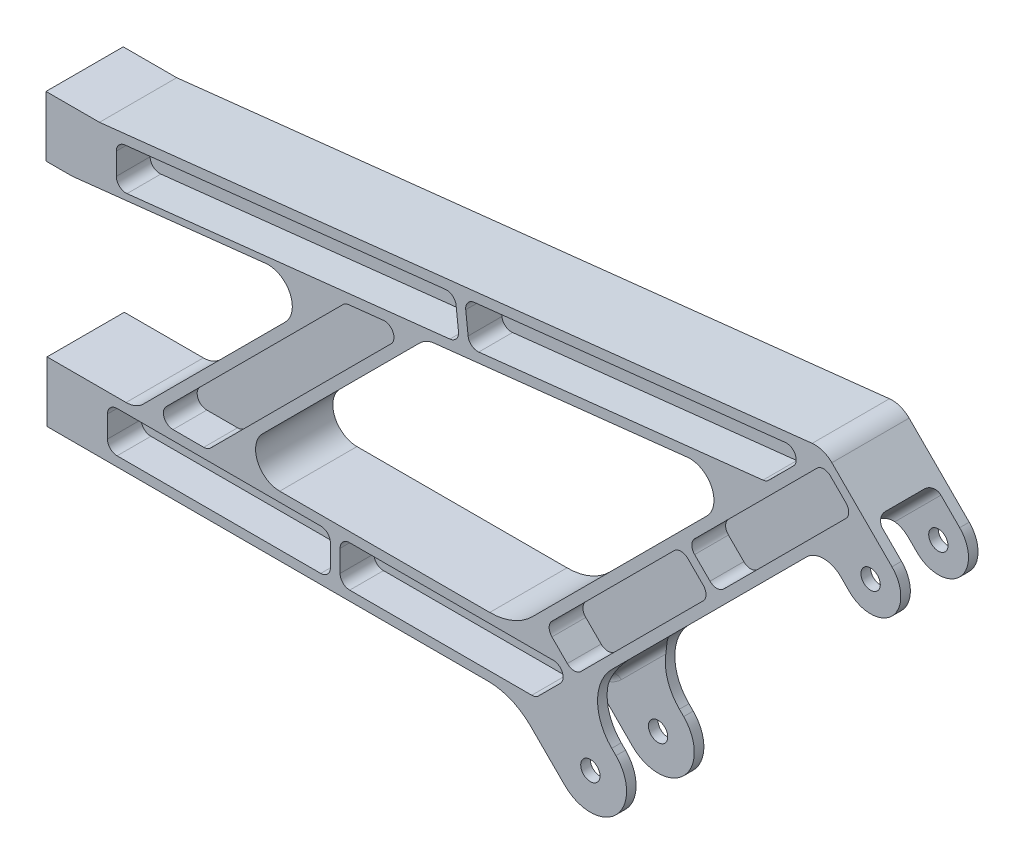
SolidWorks part; units mm, degrees
material "6061-T6 (SS)"
ref_plane "Front Plane" through (0, 0, 0) normal (0, 0, 1) x (1, 0, 0)
ref_plane "Top Plane" through (0, 0, 0) normal (0, 1, 0) x (1, 0, 0)
ref_plane "Right Plane" through (0, 0, 0) normal (1, 0, 0) x (0, 0, -1)
sketch "Sketch1" plane through (0, 0, 0) normal (0, 0, 1) x (1, 0, 0)
  line L1 (-157.7639, -90.8401) -> (-244.7728, -90.8401)
  line L2 (-67.8181, -11.2496) -> (-140.0863, -83.5177)
  line L3 (-16.0497, 33.7315) -> (8.8396, 8.8381)
  line L4 (-12.3744, -5.3033) -> (-8.8388, -8.8388)
  line L5 (-26.5165, -5.3033) -> (-107.2487, -86.0355)
  line L6 (-140.8326, -123.1624) -> (-126.6942, -137.3008)
  line L7 (-158.5102, -115.8401) -> (-341.1373, -115.8401)
  line L8 (-341.1373, -115.8401) -> (-341.1373, -90.8401)
  line L9 (-308.4124, -90.8401) -> (-341.1373, -90.8401)
  line L11 (-341.5776, -20.8403) -> (-331.2717, -20.8403)
  line L12 (-341.5776, -20.8403) -> (-341.5776, 4.1597)
  line L13 (-341.5776, 4.1597) -> (-319.4176, 4.1597)
  line L14 (-107.2487, -114.3198) -> (-105.481, -116.0876)
  line L15 (-319.4176, 4.1597) -> (-24.2138, 36.6012)
  line L17 (-301.3413, -87.9111) -> (-242.4814, -29.0512)
  line L18 (-75.9816, 5.7616) -> (-180.7131, -5.7479)
  line L19 (-251.8438, -73.769) -> (-186.6918, -8.6169)
  line L20 (-250.6448, -12.04) -> (-330.1793, -20.7804)
  arc A4 (8.8388, -8.8388) -> (8.8396, 8.8381) centre (0, 0) ccw
  arc A5 (-8.8388, -8.8388) -> (8.8388, -8.8388) centre (0, 0) ccw
  arc A6 (-12.3744, -5.3033) -> (-26.5165, -5.3033) centre (-19.4454, -12.3744) ccw
  arc A7 (-107.2487, -86.0355) -> (-107.2487, -114.3198) centre (-93.1066, -100.1777) ccw
  arc A8 (-105.481, -137.3008) -> (-105.481, -116.0876) centre (-116.0876, -126.6942) ccw
  arc A9 (-126.6942, -137.3008) -> (-105.481, -137.3008) centre (-116.0876, -126.6942) ccw
  circle A12 centre (-116.0876, -126.6942) radius 4
  circle A13 centre (0, 0) radius 4
  arc A15 (-158.5102, -115.8401) -> (-140.8326, -123.1624) centre (-158.5102, -140.8401) cw
  arc A16 (-157.7639, -90.8401) -> (-140.0863, -83.5177) centre (-157.7639, -65.8401) ccw
  arc A20 (-67.8181, -11.2496) -> (-75.9816, 5.7616) centre (-74.8892, -4.1785) ccw
  arc A21 (-16.0497, 33.7315) -> (-24.2138, 36.6012) centre (-23.1214, 26.661) ccw
  arc A22 (-186.6918, -8.6169) -> (-180.7131, -5.7479) centre (-179.6207, -15.688) cw
  arc A23 (-244.7728, -90.8401) -> (-251.8438, -73.769) centre (-244.7728, -80.8401) cw
  arc A24 (-330.1793, -20.7804) -> (-331.2717, -20.8403) centre (-331.2717, -10.8403) cw
  arc A25 (-308.4124, -90.8401) -> (-301.3413, -87.9111) centre (-308.4124, -80.8401) ccw
  arc A26 (-250.6448, -12.04) -> (-242.4814, -29.0512) centre (-249.5525, -21.9802) cw
  dimension "D2" = 25
  dimension "D3" = 25
  dimension "D7" = 10
  dimension "D6" = 25
  dimension "D1" = 25
  dimension "D4" = 25
  dimension "D5" = 25
  dimension "D8" = 119.9998
extrude "Boss-Extrude1" add sketch "Sketch1" along normal blind 32
sketch "Sketch2" plane through (0, 0, 32) normal (0, 0, 1) x (1, 0, 0)
  line L0 (-107.2487, -86.0355) -> (-26.5165, -5.3033) construction
  line L1 (-137.5386, -110.6685) -> (-128.5386, -101.6685)
  line L2 (-131.367, -94.8401) -> (-215.77, -94.8401)
  line L3 (-67.8181, -11.2496) -> (-140.0863, -83.5177) construction
  line L4 (-107.2487, -86.0355) -> (-26.5165, -5.3033)
  line L5 (-67.8181, -11.2496) -> (-140.0863, -83.5177)
  line L6 (-22.272, 28.6397) -> (-72.893, -21.9813)
  line L7 (-119.9767, -93.1066) -> (-69.3575, -42.4874)
  line L8 (-131.9975, -86.7426) -> (-125.6335, -93.1066)
  line L9 (-10.2515, 22.275) -> (-16.6149, 28.6394)
  line L10 (-64.9897, -14.078) -> (-137.2579, -86.3462) construction
  line L11 (-110.0772, -83.2071) -> (-29.3449, -2.4749) construction
  line L12 (-341.1373, -115.8401) -> (-158.5102, -115.8401) construction
  line L13 (-341.1373, -115.8401) -> (-158.5102, -115.8401)
  line L14 (-312.1373, -111.8401) -> (-227.77, -111.8401)
  line L15 (-341.1373, -111.8401) -> (-158.5102, -111.8401) construction
  line L16 (-341.1373, -90.8401) -> (-341.1373, -115.8401) construction
  line L17 (-316.1373, -98.8401) -> (-316.1373, -107.8401)
  line L18 (-157.7639, -90.8401) -> (-244.7728, -90.8401) construction
  line L19 (8.8396, 8.8381) -> (-16.0497, 33.7315) construction
  line L20 (-140.8326, -123.1624) -> (-126.6942, -137.3008) construction
  line L21 (-65.1149, -38.2448) -> (-77.1357, -26.224) construction
  line L22 (-72.893, -27.6382) -> (-66.5291, -34.0022)
  line L23 (-75.7215, -30.4666) -> (-69.3575, -36.8306)
  line L24 (-81.3783, -30.4666) -> (-131.9975, -81.0858)
  line L25 (-60.8722, -34.0022) -> (-10.2517, 16.6183)
  line L26 (-221.77, -94.8401) -> (-221.77, -111.8401) construction
  line L27 (-219.77, -98.8401) -> (-219.77, -107.8401)
  line L28 (-223.77, -98.8401) -> (-223.77, -107.8401)
  line L29 (-215.77, -111.8401) -> (-140.367, -111.8401)
  line L30 (-227.77, -94.8401) -> (-312.1373, -94.8401)
  line L38 (-308.8907, 1.2925) -> (-176.1091, 15.8845)
  line L39 (-24.2138, 36.6012) -> (-319.4176, 4.1597) construction
  line L40 (-308.0168, -15.7138) -> (-174.2521, -1.0137)
  line L41 (-75.9816, 5.7616) -> (-180.7131, -5.7479) construction
  line L42 (-312.4538, -2.6836) -> (-312.4538, -11.7378)
  line L43 (-32.0118, 24.5568) -> (-42.1838, 14.3847)
  line L44 (-170.145, 16.5399) -> (-168.288, -0.3583) construction
  line L45 (-171.6961, 12.3454) -> (-170.713, 3.3993)
  line L46 (-167.7201, 12.7824) -> (-166.7369, 3.8362)
  line L47 (-164.181, 17.1954) -> (-35.2771, 31.3613)
  line L48 (-162.3239, 0.2971) -> (-44.5753, 13.2371)
  line L49 (-218.5658, -10.7925) -> (-291.7849, -84.0116)
  line L50 (-242.4814, -29.0512) -> (-301.3413, -87.9111) construction
  line L51 (-198.6096, -14.8779) -> (-273.4002, -89.6685)
  line L52 (-186.6918, -8.6169) -> (-251.8438, -73.769) construction
  line L53 (-216.1743, -9.6449) -> (-201.875, -8.0734)
  line L54 (-288.9565, -90.8401) -> (-276.2286, -90.8401)
  line L55 (-341.5776, 4.1597) -> (-341.5776, -20.8403) construction
  arc A0 (-22.272, 28.6397) -> (-16.6149, 28.6394) centre (-19.4436, 25.8113) cw
  arc A1 (-10.2517, 16.6183) -> (-10.2515, 22.275) centre (-13.0801, 19.4468) ccw
  arc A2 (-119.9767, -93.1066) -> (-125.6335, -93.1066) centre (-122.8051, -90.2782) cw
  arc A3 (-131.9975, -81.0858) -> (-131.9975, -86.7426) centre (-129.169, -83.9142) ccw
  arc A4 (-312.1373, -111.8401) -> (-316.1373, -107.8401) centre (-312.1373, -107.8401) cw
  arc A5 (-312.1373, -94.8401) -> (-316.1373, -98.8401) centre (-312.1373, -98.8401) ccw
  arc A6 (-140.367, -111.8401) -> (-137.5386, -110.6685) centre (-140.367, -107.8401) ccw
  arc A7 (-128.5386, -101.6685) -> (-131.367, -94.8401) centre (-131.367, -98.8401) ccw
  arc A8 (-75.7215, -30.4666) -> (-81.3783, -30.4666) centre (-78.5499, -33.295) ccw
  arc A9 (-69.3575, -36.8306) -> (-69.3575, -42.4874) centre (-72.1859, -39.659) cw
  arc A10 (-66.5291, -34.0022) -> (-60.8722, -34.0022) centre (-63.7006, -31.1737) ccw
  arc A11 (-72.893, -27.6382) -> (-72.893, -21.9813) centre (-70.0646, -24.8098) cw
  arc A12 (-223.77, -107.8401) -> (-227.77, -111.8401) centre (-227.77, -107.8401) cw
  arc A13 (-219.77, -107.8401) -> (-215.77, -111.8401) centre (-215.77, -107.8401) ccw
  arc A14 (-219.77, -98.8401) -> (-215.77, -94.8401) centre (-215.77, -98.8401) cw
  arc A15 (-223.77, -98.8401) -> (-227.77, -94.8401) centre (-227.77, -98.8401) ccw
  arc A20 (-44.5753, 13.2371) -> (-42.1838, 14.3847) centre (-45.0122, 17.2132) ccw
  arc A21 (-35.2771, 31.3613) -> (-32.0118, 24.5568) centre (-34.8402, 27.3852) cw
  arc A22 (-166.7369, 3.8362) -> (-162.3239, 0.2971) centre (-162.7609, 4.2732) ccw
  arc A23 (-167.7201, 12.7824) -> (-164.181, 17.1954) centre (-163.744, 13.2193) cw
  arc A24 (-170.713, 3.3993) -> (-174.2521, -1.0137) centre (-174.6891, 2.9623) cw
  arc A25 (-171.6961, 12.3454) -> (-176.1091, 15.8845) centre (-175.6722, 11.9085) ccw
  arc A26 (-308.0168, -15.7138) -> (-312.4538, -11.7378) centre (-308.4538, -11.7378) cw
  arc A27 (-308.8907, 1.2925) -> (-312.4538, -2.6836) centre (-308.4538, -2.6836) ccw
  arc A28 (-198.6096, -14.8779) -> (-201.875, -8.0734) centre (-201.438, -12.0495) ccw
  arc A29 (-218.5658, -10.7925) -> (-216.1743, -9.6449) centre (-215.7374, -13.6209) cw
  arc A30 (-273.4002, -89.6685) -> (-276.2286, -90.8401) centre (-276.2286, -86.8401) cw
  arc A31 (-288.9565, -90.8401) -> (-291.7849, -84.0116) centre (-288.9565, -86.8401) cw
  point P34 (-316.1373, -111.8401)
  point P53 (-78.5499, -27.6382)
  point P58 (-63.7006, -36.8306)
  point P69 (-223.77, -111.8401)
  point P72 (-219.77, -111.8401)
  point P75 (-219.77, -94.8401)
  point P78 (-223.77, -94.8401)
  point P117 (-166.3, -0.1398)
  point P120 (-168.157, 16.7584)
  point P123 (-170.276, -0.5768)
  point P126 (-172.1331, 16.3215)
  dimension "D2" = 4
  dimension "D6" = 4
  dimension "D11" = 4
  dimension "D13" = 4
  dimension "D16" = 4
  dimension "D22" = 4
  dimension "D19" = 4
  dimension "D4" = 25
  dimension "D5" = 4
  dimension "D7" = 4
  dimension "D8" = 4
  dimension "D9" = 32
  dimension "D10" = 2
  dimension "D12" = 2
  dimension "D14" = 4
  dimension "D15" = 4
  dimension "D17" = 4
  dimension "D18" = 4
  dimension "D20" = 4
  dimension "D21" = 2
  dimension "D23" = 4
  dimension "D1" = 4
  dimension "D3" = 4
extrude "Cut-Extrude1" cut sketch "Sketch2" against normal blind 14 contours L38 A27 L42 A26 L40 A24 L45 A25 | A23 L46 A22 L48 A20 L43 A21 L47 | A31 L54 A30 L51 A28 L53 A29 L49 | A11 L22 A10 L25 A1 L9 A0 L6 | A9 L23 A8 L24 A3 L8 A2 L7 | A14 L27 A13 L29 A6 L1 A7 L2 | L28 A15 L30 A5 L17 A4 L14 A12 region at (-175.3079, -103.1533, 32) region at (-41.5723, -2.6814, 32) region at (-100.6775, -61.7866, 32) region at (-269.9537, -103.3401, 32) region at (-241.8227, 0.0982, 32) region at (-100.9045, 15.7508, 32) region at (-245.4094, -49.7028, 32)
ref_plane "Plane1" through (0, 0, 16) normal (0, 0, 1) x (1, 0, 0)
mirror "Mirror1" about plane through (0, 0, 16) normal (0, 0, 1) of "Cut-Extrude1"
sketch "Sketch3" plane through (0, 0, 16) normal (0, 0, 1) x (1, 0, 0)
  line L0 (-158.5102, -115.8401) -> (-141.1954, -115.8401)
  line L1 (-98.969, -77.7558) -> (-134.1243, -112.9111)
  line L2 (-107.2487, -86.0355) -> (-26.5165, -5.3033) construction
  line L3 (-158.5102, -115.8401) -> (-116.5971, -149.2186)
  line L4 (-116.5971, -149.2186) -> (-66.3597, -110.0186)
  line L5 (-66.3597, -110.0186) -> (-98.969, -77.7558)
  line L6 (-29.0156, -7.8024) -> (7.8698, 29.083)
  line L7 (7.8698, 29.083) -> (26.3533, -15.3879)
  line L8 (26.3533, -15.3879) -> (-12.041, -17.819)
  line L9 (-12.041, -17.819) -> (-29.0156, -7.8024)
  arc A0 (-134.1243, -112.9111) -> (-141.1954, -115.8401) centre (-141.1954, -105.8401) cw
  dimension "D1" = 10
extrude "Cut-Extrude2" cut sketch "Sketch3" against normal blind 12.0515 and the other way blind 12.0515
sketch "Sketch5" plane through (0, 0, 16) normal (0, 0, 1) x (1, 0, 0)
  line L0 (0, -24.7236) -> (0, -90.9031)
fillet "Fillet1" radius 4 2 edges at (-14.1417, 7.0715, 28.0515) (-14.1417, 7.0715, 3.9485)
fillet "Fillet2" radius 4 6 edges at (-149.8528, -115.8401, 3.9485) (-137.3686, -115.0789, 3.9485) (-149.8528, -115.8401, 28.0515) (-137.3686, -115.0789, 28.0515) (-120.6865, -99.4733, 3.9485) (-120.6865, -99.4733, 28.0515)
